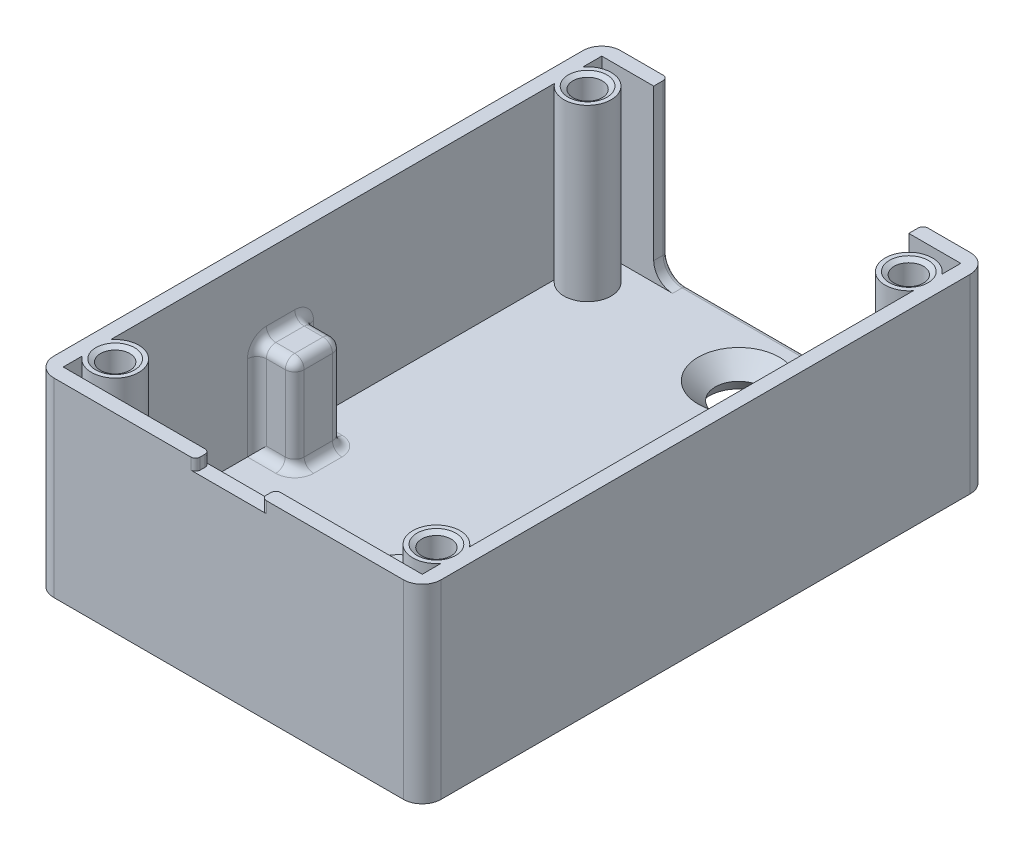
SolidWorks part; units mm, degrees
ref_plane "Спереди" through (0, 0, 0) normal (0, 0, 1) x (1, 0, 0)
ref_plane "Сверху" through (0, 0, 0) normal (0, 1, 0) x (1, 0, 0)
ref_plane "Справа" through (0, 0, 0) normal (1, 0, 0) x (0, 0, -1)
sketch "Эскиз1" plane through (0, 0, 0) normal (0, 1, 0) x (1, 0, 0)
  line L1 (-20.5, -30) -> (20.5, -30)
  line L2 (-20.5, -30) -> (-20.5, 30)
  line L3 (-20.5, 30) -> (20.5, 30)
  line L4 (20.5, -30) -> (20.5, 30)
  line L5 (0, 30) -> (0, -30) construction
  line L6 (-20.5, 0) -> (20.5, 0) construction
  circle A0 centre (0, 24) radius 2.3
  circle A1 centre (0, -24) radius 2.3
  circle A2 centre (0, -12) radius 1.9
  point P0 (0, 0)
  dimension "D1" = 48
  dimension "D2" = 4.6
  dimension "D4" = 6
  dimension "D7" = 3.8
  dimension "D8" = 42
  dimension "D3" = 60
  dimension "D5" = 41
  dimension "D6" = 12
extrude "Бобышка-Вытянуть1" add sketch "Эскиз1" along normal blind 3
chamfer "Фаска1" distance 2 angle 45 2 edges at (0, 3, 26.3) (0, 3, -21.7)
sketch "Эскиз2" plane through (0, 3, 0) normal (0, 1, 0) x (1, 0, 0)
  line L0 (-20.5, 30) -> (20.5, 30)
  line L2 (-20.5, 30) -> (-20.5, -30)
  line L3 (-20.5, -30) -> (20.5, -30)
  line L4 (20.5, 30) -> (20.5, -30)
extrude "Вытянуть-Тонкостенный1" add sketch "Эскиз2" along normal blind 18 thin
sketch "Эскиз3" plane through (0, 21, 0) normal (0, 1, 0) x (1, 0, 0)
  line L0 (0, 32.0771) -> (0, 0) construction
  line L2 (-13.5, 27.9629) -> (13.5, 27.9629)
  line L3 (-13.5, 27.9629) -> (-13.5, 30.9933)
  line L4 (-13.5, 30.9933) -> (13.5, 30.9933)
  line L5 (13.5, 27.9629) -> (13.5, 30.9933)
  line L6 (0, 30.9933) -> (0, 27.9629) construction
  line L7 (-13.5, 29.4781) -> (13.5, 29.4781) construction
  point P3 (0, 29.4781)
  dimension "D1" = 27
extrude "Вырез-Вытянуть1" cut sketch "Эскиз3" against normal up to surface (18 mm away) up to face at (0, 3, 0)
sketch "Эскиз4" plane through (0, 3, 0) normal (0, 1, 0) x (1, 0, 0)
  line L0 (0, 32.478) -> (0, 0) construction
  line L1 (0, 0) -> (39.8357, 0) construction
  line L3 (20.5, -30) -> (20.5, 30) construction
  circle A0 centre (17, 25) radius 2.5
  circle A1 centre (-17, 25) radius 2.5
  circle A2 centre (17, -25) radius 2.5
  circle A3 centre (-17, -25) radius 2.5
  dimension "D1" = 5
  dimension "D3" = 3.5
  dimension "D4" = 50
  dimension "D2" = 25
extrude "Бобышка-Вытянуть2" add sketch "Эскиз4" along normal up to surface (18 mm away) up to face at (0, 21, -9.75)
sketch "Эскиз5" plane through (0, 21, 0) normal (0, 1, 0) x (1, 0, 0)
  line L0 (20.5, -30) -> (20.5, 30) construction
  circle A0 centre (17, 25) radius 1.55
  circle A1 centre (17, -25) radius 1.55
  circle A2 centre (-17, -25) radius 1.55
  circle A3 centre (-17, 25) radius 1.55
  dimension "D1" = 3.1
  dimension "D2" = 3.5
extrude "Вырез-Вытянуть2" cut sketch "Эскиз5" against normal blind 10
sketch "Эскиз7" plane through (0, 21, 0) normal (0, 1, 0) x (1, 0, 0)
  line L1 (-3.5, -30.9828) -> (3.5, -30.9828)
  line L2 (-3.5, -30.9828) -> (-3.5, -26.6268)
  line L3 (-3.5, -26.6268) -> (3.5, -26.6268)
  line L4 (3.5, -30.9828) -> (3.5, -26.6268)
  line L5 (0, -26.6268) -> (0, -30.9828) construction
  line L6 (-3.5, -28.8048) -> (3.5, -28.8048) construction
  point P0 (0, -28.8048)
  dimension "D1" = 7
extrude "Вырез-Вытянуть3" cut sketch "Эскиз7" against normal blind 1.2
fillet "Скругление2" radius 0.5 4 edges at (-3.5, 20.4, 28.5) (-3.5, 20.4, 30) (3.5, 20.4, 30) (3.5, 20.4, 28.5)
fillet "Скругление3" radius 2 4 edges at (20.5, 10.5, -30) (-20.5, 10.5, -30) (-20.5, 10.5, 30) (20.5, 10.5, 30)
chamfer "Фаска4" distance 1.5 angle 30 11 edges at (0, 0, 26.3) (0, 0, -30) (-20.5, 0, 0) (0, 0, 30) (20.5, 0, 0) (0, 0, -21.7) (-19.9142, 0, -29.4142) (-19.9142, 0, 29.4142) (19.9142, 0, 29.4142) (19.9142, 0, -29.4142) (0, 0, 13.9)
chamfer "Фаска6" distance 0.5 angle 30 4 edges at (-17, 21, -23.45) (-17, 21, 26.55) (17, 21, 26.55) (17, 21, -23.45)
sketch "Эскиз8" plane through (0, 3, 0) normal (0, 1, 0) x (1, 0, 0)
  line L0 (-24.1981, 0) -> (27.887, 0) construction
  line L1 (19, -23.5) -> (19, 23.5) construction
  line L2 (19, -11.5) -> (15, -11.5)
  line L3 (19, -11.5) -> (19, -16.5)
  line L4 (19, -16.5) -> (15, -16.5)
  line L5 (15, -11.5) -> (15, -16.5)
  line L6 (-19, 23.5) -> (-19, -23.5) construction
  line L7 (-19, -3) -> (-15, -3)
  line L8 (-19, -3) -> (-19, -8)
  line L9 (-19, -8) -> (-15, -8)
  line L10 (-15, -3) -> (-15, -8)
  dimension "D1" = 11.5
  dimension "D2" = 4
  dimension "D3" = 5
  dimension "D4" = 3
  dimension "D5" = 5
  dimension "D6" = 4
extrude "Бобышка-Вытянуть3" add sketch "Эскиз8" along normal blind 10
fillet "Скругление6" radius 1 22 edges at (-17, 3, 8) (-17, 3, 3) (-19, 8, 3) (-19, 8, 8) (17, 3, 11.5) (17, 3, 16.5) (-15, 8, 8) (-15, 8, 3) (-15, 3, 5.5) (-17, 13, 3) (-15, 13, 5.5) (-17, 13, 8) (-19, 13, 5.5) (17, 13, 16.5) (17, 13, 11.5) (19, 13, 14) (15, 8, 11.5) (15, 13, 14) (15, 8, 16.5) (15, 3, 14) (19, 8, 16.5) (19, 8, 11.5)
fillet "Скругление7" radius 2 2 edges at (13.5, 3, -29.25) (-13.5, 3, -29.25)
fillet "Скругление8" radius 0.5 5 edges at (13.5, 13, -30) (12.9142, 3.5858, -30) (0, 3, -30) (-12.9142, 3.5858, -30) (-13.5, 13, -30)
chamfer "Фаска7" distance 1 angle 45 1 edges at (0, 3, 13.9)
